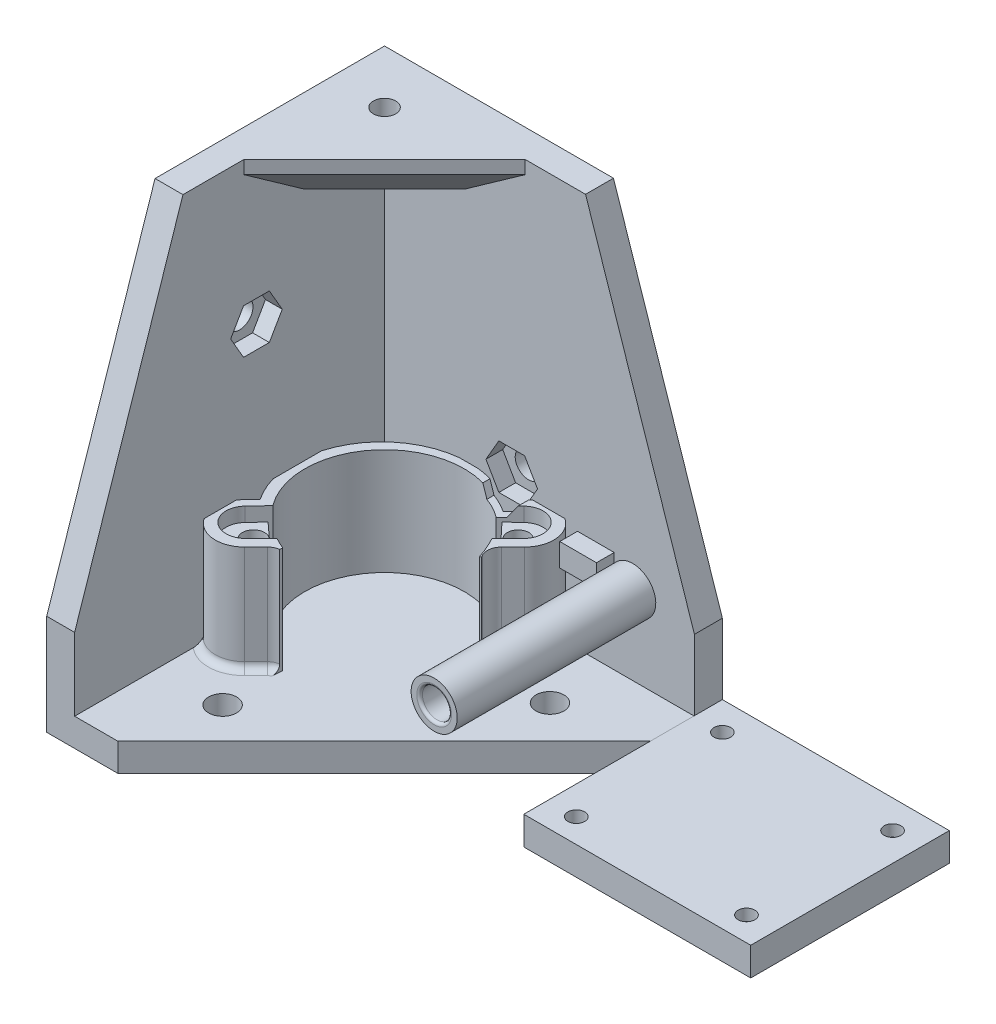
SolidWorks part; units mm, degrees
ref_plane "Front" through (0, 0, 0) normal (0, 0, 1) x (1, 0, 0)
ref_plane "Top" through (0, 0, 0) normal (0, 1, 0) x (1, 0, 0)
ref_plane "Right" through (0, 0, 0) normal (1, 0, 0) x (0, 0, -1)
sketch "Sketch1" plane through (0, 0, 0) normal (0, 1, 0) x (1, 0, 0)
  line L0 (0, 0) -> (0, 60.5)
  line L1 (0, -55) -> (0, 55) construction
  line L2 (0, 60.5) -> (60.5, 60.5)
  line L3 (60.5, 60.5) -> (60.5, 47.75)
  line L4 (60.5, 47.75) -> (12.75, 0)
  line L5 (-55, 0) -> (55, 0) construction
  line L6 (12.75, 0) -> (0, 0)
  dimension "D1" = 60.5
  dimension "D2" = 12.75
extrude "Boss-Extrude1" add sketch "Sketch1" along normal blind 5
sketch "Sketch4" plane through (0, 0, 0) normal (-1, 0, 0) x (0, 0, 1)
  line L0 (-60.5, 5) -> (-60.5, 76.1962)
  line L1 (-60.5, 76.1962) -> (-19.4, 76.1962)
  line L2 (-19.4, 76.1962) -> (0, 18.0048)
  line L3 (0, 18.0048) -> (0, 5)
  line L4 (0, -37.675) -> (0, 37.675) construction
  line L5 (-60.5, 5) -> (0, 5) construction
  line L6 (-60.5, 5) -> (0, 5)
  dimension "D1" = 71.1962
  dimension "D2" = 41.1
  dimension "D3" = 61.34
extrude "Boss-Extrude2" add sketch "Sketch4" against normal blind 5
sketch "Sketch5" plane through (0, 0, -60.5) normal (0, 0, -1) x (-1, 0, 0)
  line L0 (0, 76.1962) -> (-41, 76.1962)
  line L1 (-41, 76.1962) -> (-60.5, 17.7009)
  line L2 (-60.5, 17.7009) -> (-60.5, 5)
  line L6 (-60.5, 0) -> (0, 0)
  line L7 (0, 0) -> (0, 76.1962)
  line L8 (0, 76.1962) -> (-5, 76.1962)
  line L9 (-5, 76.1962) -> (-5, 5)
  line L10 (-5, 5) -> (-60.5, 5)
  line L11 (-60.5, 5) -> (-60.5, 0)
  line L12 (-60.5, 0) -> (0, 0)
  line L13 (0, 0) -> (0, 76.1962)
  line L14 (0, 76.1962) -> (-5, 76.1962)
  line L15 (-5, 76.1962) -> (-5, 5)
  line L16 (-5, 5) -> (-60.5, 5)
  line L17 (-60.5, 5) -> (-60.5, 0)
  line M13 (-5, 76.1962) -> (-5, 5)
  line M14 (-5, 5) -> (-60.5, 5)
  dimension "D2" = 41
  dimension "D3" = 61.66
  dimension "D1" = 0
extrude "Boss-Extrude3" add sketch "Sketch5" against normal blind 5 contours L1 L2 L0 M14 M13 region at (29.1655, 37.8824, -60.5)
sketch "Sketch6" plane through (0, 5, 0) normal (0, 1, 0) x (1, 0, 0)
  line L0 (60.5, 60.5) -> (0, 60.5) construction
  line L4 (0, 19.4) -> (0, 0)
  line L5 (60.5, 55.5) -> (5, 55.5)
  line L6 (5, 55.5) -> (5, 0)
  line L7 (5, 0) -> (12.75, 0)
  line L8 (12.75, 0) -> (60.5, 47.75)
  line L9 (60.5, 47.75) -> (60.5, 55.5)
  line L10 (60.5, 55.5) -> (5, 55.5)
  line L11 (5, 55.5) -> (5, 0)
  line L12 (5, 0) -> (12.75, 0)
  line L13 (12.75, 0) -> (60.5, 47.75)
  line L14 (60.5, 47.75) -> (60.5, 55.5)
  line L15 (0, 0) -> (5, 0)
  line L16 (5, 0) -> (5, 19.4)
  line L17 (5, 19.4) -> (0, 19.4)
  line L18 (0, 19.4) -> (0, 0)
  line L19 (0, 0) -> (5, 0)
  line L20 (5, 0) -> (5, 19.4)
  line L21 (5, 19.4) -> (0, 19.4)
  line L24 (0, 60.5) -> (0, 19.4)
  line L25 (0, 19.4) -> (5, 19.4)
  line L26 (5, 19.4) -> (5, 55.5)
  line L27 (5, 55.5) -> (41, 55.5)
  line L28 (41, 55.5) -> (41, 60.5)
  line L29 (41, 60.5) -> (0, 60.5)
  line L30 (0, 60.5) -> (0, 19.4)
  line L31 (0, 19.4) -> (5, 19.4)
  line L32 (5, 19.4) -> (5, 55.5)
  line L33 (5, 55.5) -> (41, 55.5)
  line L34 (41, 55.5) -> (41, 60.5)
  line L35 (41, 60.5) -> (0, 60.5)
  circle A0 centre (16.5, 15) radius 2.5
  circle A1 centre (45.5, 44.625) radius 2.5
  dimension "D1" = 5
  dimension "D2" = 5
  dimension "D3" = 0
  dimension "D4" = 15
  dimension "D6" = 16.5
  dimension "D7" = 15
  dimension "D9" = 15.875
  dimension "D5" = 0
  dimension "D8" = 0
extrude "Cut-Extrude1" cut sketch "Sketch6" against normal through all contours A0 | A1 region at (16.5, 5, -15) region at (45.5, 5, -44.625)
sketch "Sketch9" plane through (0, 0, -55.5) normal (0, 0, 1) x (1, 0, 0)
  line L1 (5, 76.1962) -> (5, 5) construction
  line L5 (0, 0) -> (60.5, 0)
  line L6 (0, 76.1962) -> (0, 0)
  line L7 (41, 76.1962) -> (0, 76.1962)
  line L8 (60.5, 17.7009) -> (41, 76.1962)
  line L9 (60.5, 0) -> (60.5, 17.7009)
  line L10 (0, 0) -> (60.5, 0)
  line L11 (0, 76.1962) -> (0, 0)
  line L12 (41, 76.1962) -> (0, 76.1962)
  line L13 (60.5, 17.7009) -> (41, 76.1962)
  line L14 (60.5, 0) -> (60.5, 17.7009)
  line L15 (49.45, 19.0462) -> (49.45, 3.6199) construction
  circle A0 centre (49.45, 19.0462) radius 4.1275
  circle A1 centre (49.45, 19.0462) radius 2.6035
  dimension "D2" = 5.207
  dimension "D3" = 1.524
  dimension "D4" = 57.15
  dimension "D5" = 44.45
  dimension "D1" = 0
extrude "Boss-Extrude5" add sketch "Sketch9" along normal blind 35.56 contours A1 A0 region at (45.4392, 19.0462, -55.5)
fillet "Fillet1" radius 0.508 1 edges at (52.0535, 19.0462, -19.94)
sketch "Sketch14" plane through (0, 5, 0) normal (0, 1, 0) x (1, 0, 0)
  line L0 (13.4627, 27.5396) -> (14.7681, 26.7924)
  line L1 (12.75, 0) -> (60.5, 47.75) construction
  line L2 (36.625, 23.875) -> (5, 55.5) construction
  line L3 (5, 55.5) -> (60.5, 55.5) construction
  line L4 (32.9604, 47.0373) -> (33.7076, 45.7319)
  line L5 (14.8281, 26.8523) -> (11.8274, 23.8516)
  line L6 (6.723, 28.8027) -> (9.1327, 31.3641)
  line L7 (33.6477, 45.6719) -> (36.6484, 48.6726)
  line L8 (31.6973, 53.777) -> (29.1359, 51.3673)
  line L9 (15.0744, 24.4582) -> (13.006, 22.3898)
  line L10 (5.6561, 29.7396) -> (7.0609, 31.1444)
  line L11 (36.0418, 45.4256) -> (38.1102, 47.494)
  line L12 (30.7604, 54.8439) -> (28.83, 52.9135)
  line L13 (18.1324, 24.8665) -> (30.5234, 17.7734)
  line L14 (35.6335, 42.3676) -> (42.7266, 29.9766)
  line L15 (31.7409, 18.9909) -> (18.852, 25.7543)
  line L16 (41.5091, 28.7591) -> (34.7457, 41.648)
  line L17 (16.5689, 25.6946) -> (16.5343, 25.1798)
  line L18 (34.7457, 41.648) -> (35.7996, 42.0774)
  circle A0 centre (20.5607, 39.9393) radius 14.2875
  arc A1 (11.8274, 23.8516) -> (6.723, 28.8027) centre (9.3129, 26.3661) cw
  arc A2 (36.6484, 48.6726) -> (31.6973, 53.777) centre (34.1339, 51.1871) ccw
  arc A3 (13.006, 22.3898) -> (5.6561, 29.7396) centre (9.3311, 26.0647) cw
  arc A4 (38.1102, 47.494) -> (30.7604, 54.8439) centre (34.4353, 51.1689) ccw
  arc A5 (7.0609, 31.1444) -> (28.83, 52.9135) centre (20.0709, 39.9035) cw
  arc A6 (36.0418, 45.4256) -> (35.6335, 42.3676) centre (37.8378, 43.6295) ccw
  arc A7 (15.0744, 24.4582) -> (18.1324, 24.8665) centre (16.8705, 22.6622) cw
  arc A9 (33.8602, 45.8844) -> (36.3595, 38.5726) centre (13.6025, 34.877) cw
  arc A10 (14.6156, 26.6398) -> (21.9274, 24.1405) centre (25.623, 46.8975) ccw
  point P40 (34.6689, 44.0527)
  point P43 (16.4473, 25.8311)
  line M13 (60.5, 55.5) -> (5, 55.5)
  line M14 (5, 55.5) -> (5, 0)
  line M16 (12.75, 0) -> (60.5, 47.75)
  dimension "D1" = 28.575
  dimension "D2" = 3.556
  dimension "D3" = 2.54
extrude "Boss-Extrude6" add sketch "Sketch14" along normal blind 19.05 contours L2 A0 L5 A1 L6 A5 L10 A3 L9 A7 L13 M16 M14 | L2 L14 A6 L11 A4 L12 A5 A0 L8 A2 L7 M16 M13 region at (7.691, 5, -30.3062) region at (10.0875, 5, -50.8829)
sketch "Sketch15" plane through (0, 76.1962, 0) normal (0, 1, 0) x (1, 0, 0)
  line L0 (5, 30.3375) -> (30.1625, 55.5)
  line L1 (0, -33.275) -> (0, 33.275) construction
  line L2 (41, 60.5) -> (0, 60.5) construction
  line L6 (0, 60.5) -> (0, 19.4)
  line L7 (0, 19.4) -> (5, 19.4)
  line L8 (5, 19.4) -> (5, 55.5)
  line L9 (5, 55.5) -> (41, 55.5)
  line L10 (41, 55.5) -> (41, 60.5)
  line L11 (41, 60.5) -> (0, 60.5)
  line L13 (0, 19.4) -> (5, 19.4)
  line L14 (5, 30.3375) -> (5, 55.5)
  line L15 (5, 55.5) -> (30.1625, 55.5)
  line L16 (41, 55.5) -> (41, 60.5)
  circle A0 centre (9.525, 50.975) radius 2
  line M11 (5, 19.4) -> (5, 55.5)
  line M12 (5, 55.5) -> (41, 55.5)
  dimension "D3" = 4
  dimension "D4" = 9.525
  dimension "D5" = 9.525
  dimension "D2" = 45
  dimension "D1" = 0
extrude "Boss-Extrude7" add sketch "Sketch15" against normal blind 10 contours L0 A0 M11 M12 region at (13.5472, 76.1962, -46.9528)
chamfer "Chamfer2" distance 7.62 angle 45 1 edges at (17.5813, 66.1962, -42.9187)
fillet "Fillet2" radius 1.27 7 edges at (39.6065, 5, -51.6871) (37.076, 5, -46.4598) (35.3202, 5, -43.9657) (8.8129, 5, -20.8935) (14.0402, 5, -23.424) (15.745, 5, -24.9392) (35.7165, 5, -42.2225)
sketch "Sketch16" plane through (0, 0, -55.5) normal (0, 0, 1) x (1, 0, 0)
  line L1 (46.1305, 23.2107) -> (38.2864, 23.2107)
  line L2 (46.1305, 23.2107) -> (46.1305, 19.0978)
  line L3 (46.1305, 19.0978) -> (38.2864, 19.0978)
  line L4 (38.2864, 23.2107) -> (38.2864, 19.0978)
extrude "Boss-Extrude8" add sketch "Sketch16" along normal blind 3.175
chamfer "Chamfer3" distance 1.27 angle 45 1 edges at (38.2864, 23.2107, -55.0794)
sketch "Sketch17" plane through (0, 5, 0) normal (0, 1, 0) x (1, 0, 0)
  line L0 (8.716, 30.9212) -> (14.047, 26.0712)
  line L1 (36.625, 23.875) -> (5, 55.5) construction
  line L2 (12.75, 0) -> (60.5, 47.75) construction
  line L3 (5, 55.5) -> (18.418, 55.5) construction
  line L4 (5, 55.5) -> (5, 44.2452) construction
  line L5 (29.6632, 51.8634) -> (34.5959, 46.6202)
  line L22 (37.3079, 55.5) -> (31.5627, 55.5)
  line L23 (30.7604, 54.8439) -> (28.83, 52.9135)
  line L24 (21.7238, 55.5) -> (18.418, 55.5)
  line L25 (5, 44.2452) -> (5, 35.5618)
  line L26 (7.0609, 31.1444) -> (5.6561, 29.7396)
  line L27 (5, 28.9373) -> (5, 23.1921)
  line L28 (13.006, 22.3898) -> (15.0744, 24.4582)
  line L29 (16.5343, 25.1798) -> (16.5689, 25.6946)
  line L30 (16.5343, 25.1798) -> (16.5689, 25.6946)
  line L31 (35.539, 41.9712) -> (35.7996, 42.0774)
  line L32 (35.539, 41.9712) -> (35.7996, 42.0774)
  line L33 (14.6156, 26.6398) -> (11.8274, 23.8516)
  line L34 (6.723, 28.8027) -> (9.1327, 31.3641)
  line L35 (29.1359, 51.3673) -> (31.6973, 53.777)
  line L36 (36.6484, 48.6726) -> (33.8602, 45.8844)
  line L40 (35.7996, 42.0774) -> (35.6335, 42.3676)
  line L41 (36.0418, 45.4256) -> (38.1102, 47.494)
  line L43 (37.3079, 55.5) -> (31.5627, 55.5)
  line L44 (30.7604, 54.8439) -> (28.83, 52.9135)
  line L45 (21.7238, 55.5) -> (18.418, 55.5)
  line L46 (5, 44.2452) -> (5, 35.5618)
  line L47 (7.0609, 31.1444) -> (5.6561, 29.7396)
  line L48 (5, 28.9373) -> (5, 23.1921)
  line L49 (13.006, 22.3898) -> (15.0744, 24.4582)
  line L54 (14.6156, 26.6398) -> (11.8274, 23.8516)
  line L55 (6.723, 28.8027) -> (9.1327, 31.3641)
  line L56 (29.1359, 51.3673) -> (31.6973, 53.777)
  line L57 (36.6484, 48.6726) -> (33.8602, 45.8844)
  line L61 (35.7996, 42.0774) -> (35.6335, 42.3676)
  line L62 (36.0418, 45.4256) -> (38.1102, 47.494)
  circle A1 centre (33.6908, 50.7324) radius 2.1828
  circle A2 centre (10.0204, 27.0078) radius 1.9844
  circle A3 centre (33.6908, 50.7324) radius 1.9288
  arc A15 (38.1102, 47.494) -> (37.3079, 55.5) centre (34.4353, 51.1689) ccw
  arc A17 (31.5627, 55.5) -> (30.7604, 54.8439) centre (34.4353, 51.1689) ccw
  arc A18 (28.83, 52.9135) -> (21.7238, 55.5) centre (20.0709, 39.9035) ccw
  arc A19 (18.418, 55.5) -> (5, 44.2452) centre (20.0709, 39.9035) ccw
  arc A20 (5, 35.5618) -> (7.0609, 31.1444) centre (20.0709, 39.9035) ccw
  arc A21 (5.6561, 29.7396) -> (5, 28.9373) centre (9.3311, 26.0647) ccw
  arc A22 (5, 23.1921) -> (13.006, 22.3898) centre (9.3311, 26.0647) ccw
  arc A23 (16.5343, 25.1798) -> (15.0744, 24.4582) centre (16.8705, 22.6622) ccw
  arc A24 (14.6156, 26.6398) -> (16.5689, 25.6946) centre (25.623, 46.8975) ccw
  arc A25 (6.723, 28.8027) -> (11.8274, 23.8516) centre (9.3129, 26.3661) ccw
  arc A26 (29.1359, 51.3673) -> (9.1327, 31.3641) centre (20.5607, 39.9393) ccw
  arc A27 (36.6484, 48.6726) -> (31.6973, 53.777) centre (34.1339, 51.1871) ccw
  arc A28 (35.539, 41.9712) -> (33.8602, 45.8844) centre (13.6025, 34.877) ccw
  arc A29 (36.0418, 45.4256) -> (35.6335, 42.3676) centre (37.8378, 43.6295) ccw
  arc A30 (38.1102, 47.494) -> (37.3079, 55.5) centre (34.4353, 51.1689) ccw
  arc A32 (31.5627, 55.5) -> (30.7604, 54.8439) centre (34.4353, 51.1689) ccw
  arc A33 (28.83, 52.9135) -> (21.7238, 55.5) centre (20.0709, 39.9035) ccw
  arc A34 (18.418, 55.5) -> (5, 44.2452) centre (20.0709, 39.9035) ccw
  arc A35 (5, 35.5618) -> (7.0609, 31.1444) centre (20.0709, 39.9035) ccw
  arc A36 (5.6561, 29.7396) -> (5, 28.9373) centre (9.3311, 26.0647) ccw
  arc A37 (5, 23.1921) -> (13.006, 22.3898) centre (9.3311, 26.0647) ccw
  arc A38 (16.5343, 25.1798) -> (15.0744, 24.4582) centre (16.8705, 22.6622) ccw
  arc A39 (14.6156, 26.6398) -> (16.5689, 25.6946) centre (25.623, 46.8975) ccw
  arc A40 (6.723, 28.8027) -> (11.8274, 23.8516) centre (9.3129, 26.3661) ccw
  arc A41 (29.1359, 51.3673) -> (9.1327, 31.3641) centre (20.5607, 39.9393) ccw
  arc A42 (36.6484, 48.6726) -> (31.6973, 53.777) centre (34.1339, 51.1871) ccw
  arc A43 (35.539, 41.9712) -> (33.8602, 45.8844) centre (13.6025, 34.877) ccw
  arc A44 (36.0418, 45.4256) -> (35.6335, 42.3676) centre (37.8378, 43.6295) ccw
  line M44 (33.8602, 45.8844) -> (36.6484, 48.6726)
  arc M45 (36.6484, 48.6726) -> (31.6973, 53.777) centre (34.1339, 51.1871) ccw
  line M46 (31.6973, 53.777) -> (29.1359, 51.3673)
  line M48 (9.1327, 31.3641) -> (6.723, 28.8027)
  arc M49 (6.723, 28.8027) -> (11.8274, 23.8516) centre (9.3129, 26.3661) ccw
  line M50 (11.8274, 23.8516) -> (14.6156, 26.6398)
  dimension "D2" = 3.9688
  dimension "D3" = 0.254
  dimension "D1" = 0
extrude "Boss-Extrude9" add sketch "Sketch17" along normal offset from surface (16.51 mm away) 2.54 contours L5 A1 M46 M44 M45 | L0 M48 M49 M50 | A1 L5 A3 region at (11.3737, 5, -28.4876) region at (30.7585, 5, -52.737) region at (33.0584, 5, -52.7569) up to face at (20.9693, 24.05, -39.9839)
sketch "Sketch18" plane through (0, 0, 0) normal (-1, 0, 0) x (0, 0, 1)
  line L0 (-60.5, 76.1962) -> (-60.5, 0) construction
  line L1 (33.275, 0) -> (-33.275, 0) construction
  circle A0 centre (-32.56, 49.53) radius 2.3813
  dimension "D1" = 27.94
  dimension "D2" = 49.53
  dimension "D3" = 4.7625
extrude "Cut-Extrude2" cut sketch "Sketch18" against normal up to next
sketch "Sketch19" plane through (0, 0, -60.5) normal (0, 0, -1) x (-1, 0, 0)
  line L0 (0, 33.275) -> (0, -33.275) construction
  line L1 (33.275, 0) -> (-33.275, 0) construction
  circle A0 centre (-27.7812, 26.1937) radius 2.3813
  dimension "D1" = 27.7812
  dimension "D2" = 26.1937
  dimension "D3" = 4.7625
extrude "Cut-Extrude3" cut sketch "Sketch19" against normal up to next
sketch "Sketch20" plane through (0, 0, -55.5) normal (0, 0, 1) x (1, 0, 0)
  line L1 (32.4001, 26.1938) -> (30.0907, 30.1938)
  line L2 (30.0907, 30.1938) -> (25.4718, 30.1938)
  line L3 (25.4718, 30.1938) -> (23.1624, 26.1938)
  line L4 (23.1624, 26.1938) -> (25.4718, 22.1938)
  line L5 (25.4718, 22.1938) -> (30.0907, 22.1938)
  line L6 (30.0907, 22.1938) -> (32.4001, 26.1938)
  circle A0 centre (27.7812, 26.1937) radius 2.3813 construction
  circle A1 centre (27.7812, 26.1937) radius 2.3813
  circle A2 centre (27.7812, 26.1937) radius 4 construction
  dimension "D1" = 8
extrude "Cut-Extrude4" cut sketch "Sketch20" against normal blind 3 and the other way up to vertex (4.1327 mm away) contours L1 L2 L3 L4 L5 L6 other way up to point (29.1359, 24.05, -51.3673)
sketch "Sketch21" plane through (5, 0, 0) normal (1, 0, 0) x (0, 0, -1)
  line L1 (34.8694, 53.53) -> (30.2506, 53.53)
  line L2 (30.2506, 53.53) -> (27.9412, 49.53)
  line L3 (27.9412, 49.53) -> (30.2506, 45.53)
  line L4 (30.2506, 45.53) -> (34.8694, 45.53)
  line L5 (34.8694, 45.53) -> (37.1788, 49.53)
  line L6 (37.1788, 49.53) -> (34.8694, 53.53)
  circle A0 centre (32.56, 49.53) radius 2.3813 construction
  circle A1 centre (32.56, 49.53) radius 2.3812
  circle A2 centre (32.56, 49.53) radius 4 construction
  dimension "D1" = 8
extrude "Cut-Extrude5" cut sketch "Sketch21" against normal blind 3 contours L1 L2 L3 L4 L5 L6
sketch "Sketch23" plane through (0, 0, 0) normal (0, 1, 0) x (1, 0, 0)
  line L1 (60.5, 60.5) -> (101.14, 60.5)
  line L2 (60.5, 60.5) -> (60.5, 24.94)
  line L3 (60.5, 24.94) -> (101.14, 24.94)
  line L4 (101.14, 60.5) -> (101.14, 24.94)
  dimension "D1" = 40.64
  dimension "D2" = 35.56
extrude "Boss-Extrude12" add sketch "Sketch23" along normal blind 5.08
sketch "Sketch24" plane through (0, 5.08, 0) normal (0, 1, 0) x (1, 0, 0)
  line L0 (101.14, 60.5) -> (60.5, 60.5) construction
  line L1 (60.5, 47.75) -> (60.5, 55.5) construction
  circle A0 centre (65.58, 55.42) radius 1.5
  circle A1 centre (96.06, 55.42) radius 1.5
  circle A2 centre (96.06, 29.258) radius 1.5
  circle A3 centre (65.58, 29.258) radius 1.5
  dimension "D1" = 3
  dimension "D2" = 26.162
  dimension "D3" = 30.48
  dimension "D4" = 5.08
  dimension "D5" = 5.08
extrude "Cut-Extrude6" cut sketch "Sketch24" against normal up to next
sketch "Sketch25" plane through (0, 0, 0) normal (0, -1, 0) x (1, 0, 0)
  line L1 (67.2399, -32.133) -> (68.8998, -29.258)
  line L2 (68.8998, -29.258) -> (67.2399, -26.383)
  line L3 (67.2399, -26.383) -> (63.9201, -26.383)
  line L4 (63.9201, -26.383) -> (62.2602, -29.258)
  line L5 (62.2602, -29.258) -> (63.9201, -32.133)
  line L6 (63.9201, -32.133) -> (67.2399, -32.133)
  line L7 (94.4001, -32.133) -> (97.7199, -32.133)
  line L8 (97.7199, -32.133) -> (99.3798, -29.258)
  line L9 (99.3798, -29.258) -> (97.7199, -26.383)
  line L10 (97.7199, -26.383) -> (94.4001, -26.383)
  line L11 (94.4001, -26.383) -> (92.7402, -29.258)
  line L12 (92.7402, -29.258) -> (94.4001, -32.133)
  line L13 (92.7402, -55.42) -> (94.4001, -58.295)
  line L14 (94.4001, -58.295) -> (97.7199, -58.295)
  line L15 (97.7199, -58.295) -> (99.3798, -55.42)
  line L16 (99.3798, -55.42) -> (97.7199, -52.545)
  line L17 (97.7199, -52.545) -> (94.4001, -52.545)
  line L18 (94.4001, -52.545) -> (92.7402, -55.42)
  line L19 (68.8998, -55.42) -> (67.2399, -52.545)
  line L20 (67.2399, -52.545) -> (63.9201, -52.545)
  line L21 (63.9201, -52.545) -> (62.2602, -55.42)
  line L22 (62.2602, -55.42) -> (63.9201, -58.295)
  line L23 (63.9201, -58.295) -> (67.2399, -58.295)
  line L24 (67.2399, -58.295) -> (68.8998, -55.42)
  circle A0 centre (65.58, -29.258) radius 1.5 construction
  circle A1 centre (65.58, -29.258) radius 1.5
  circle A2 centre (96.06, -29.258) radius 1.5 construction
  circle A3 centre (96.06, -29.258) radius 1.5
  circle A4 centre (65.58, -55.42) radius 1.5 construction
  circle A5 centre (65.58, -55.42) radius 1.5
  circle A6 centre (96.06, -55.42) radius 1.5 construction
  circle A7 centre (96.06, -55.42) radius 1.5
  circle A8 centre (65.58, -29.258) radius 2.875 construction
  circle A9 centre (96.06, -29.258) radius 2.875 construction
  circle A10 centre (96.06, -55.42) radius 2.875 construction
  circle A11 centre (65.58, -55.42) radius 2.875 construction
  dimension "D1" = 5.75
  dimension "D2" = 5.75
  dimension "D3" = 5.75
  dimension "D4" = 5.75
extrude "Cut-Extrude7" cut sketch "Sketch25" against normal blind 3
sketch "Sketch26" plane through (0, 66.1962, 0) normal (0, -1, 0) x (1, 0, 0)
  line L1 (13.0753, -53.024) -> (13.0747, -48.9248)
  line L2 (13.0747, -48.9248) -> (9.5243, -46.8758)
  line L3 (9.5243, -46.8758) -> (5.9747, -48.926)
  line L4 (5.9747, -48.926) -> (5.9753, -53.0252)
  line L5 (5.9753, -53.0252) -> (9.5257, -55.0742)
  line L6 (9.5257, -55.0742) -> (13.0753, -53.024)
  circle A0 centre (9.525, -50.975) radius 2 construction
  circle A1 centre (9.525, -50.975) radius 2
  circle A2 centre (9.525, -50.975) radius 3.55 construction
  point P3 (13.0747, -53.0252)
  dimension "D1" = 7.1
extrude "Cut-Extrude8" cut sketch "Sketch26" against normal blind 3.5
